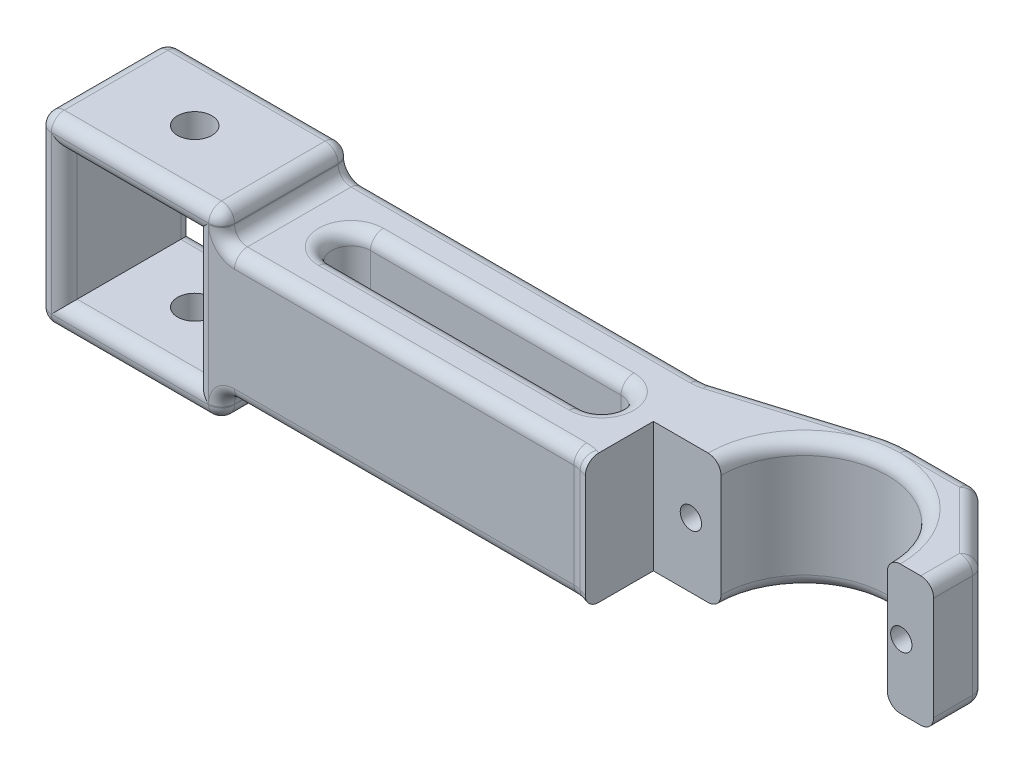
SolidWorks part; units mm, degrees
ref_plane "Front Plane" through (0, 0, 0) normal (0, 0, 1) x (1, 0, 0)
ref_plane "Top Plane" through (0, 0, 0) normal (0, 1, 0) x (1, 0, 0)
ref_plane "Right Plane" through (0, 0, 0) normal (1, 0, 0) x (0, 0, -1)
sketch "Sketch1" plane through (0, 0, 0) normal (0, 0, 1) x (1, 0, 0)
  line L1 (-10.15, -10.15) -> (10.15, -10.15)
  line L2 (-10.15, -10.15) -> (-10.15, 10.15)
  line L3 (-10.15, 10.15) -> (10.15, 10.15)
  line L4 (10.15, -10.15) -> (10.15, 10.15)
  line L5 (-10.15, -10.15) -> (10.15, 10.15) construction
  line L6 (-10.15, 10.15) -> (10.15, -10.15) construction
  point P0 (0, 0)
  dimension "D1" = 20.3
extrude "Extrude-Thin1" add sketch "Sketch1" along normal mid plane 20 thin thin type one direction wall 4
sketch "Sketch2" plane through (0, 0, 0) normal (0, 1, 0) x (1, 0, 0)
  line L3 (14.15, -10) -> (14.15, 10) construction
  line L4 (14.15, 10) -> (69.15, 10)
  line L5 (14.15, 10) -> (14.15, -10)
  line L6 (14.15, -10) -> (69.15, -10)
  line L7 (69.15, 10) -> (69.15, -10)
  line L9 (0, 0) -> (94.15, 0) construction
  line L10 (69.15, -10) -> (89.2407, -16.119)
  line L13 (69.15, 10) -> (89.2407, 16.119)
  line L15 (69.15, -10) -> (69.15, 10)
  circle A2 centre (94.15, 0) radius 12.85
  arc A3 (89.2407, -16.119) -> (89.2407, 16.119) centre (94.15, 0) ccw
  circle A4 centre (94.15, 0) radius 16.85 construction
  dimension "D1" = 25.7
  dimension "D2" = 4
  dimension "D3" = 80
  dimension "D4" = 25
extrude "Boss-Extrude4" add sketch "Sketch2" along normal mid plane 20 contours L7 L4 L5 L6 | L10 A3 L13 L7 A2 region at (41.65, 0, 0) region at (79.3519, 0, -12.5455)
sketch "Sketch3" plane through (0, 0, 0) normal (0, 1, 0) x (1, 0, 0)
  line L0 (94.15, 16.85) -> (114.15, 16.85)
  line L1 (114.15, 16.85) -> (114.15, -16.85)
  line L2 (114.15, -16.85) -> (94.15, -16.85)
  line L3 (14.15, -10) -> (14.15, 10) construction
  arc A1 (94.15, -16.85) -> (94.15, 16.85) centre (94.15, 0) ccw
  arc A2 (89.2407, -16.119) -> (89.2407, 16.119) centre (94.15, 0) ccw construction
  dimension "D1" = 100
extrude "Boss-Extrude5" add sketch "Sketch3" along normal mid plane 20
sketch "Sketch4" plane through (0, 0, 0) normal (0, -1, 0) x (1, 0, 0)
  line L9 (104.15, 16.85) -> (114.15, 16.85)
  line L10 (94.15, 16.85) -> (114.15, 16.85) construction
  line L11 (114.15, 16.85) -> (114.15, 6.85)
  line L12 (114.15, 16.85) -> (114.15, -16.85) construction
  line L13 (114.15, 6.85) -> (104.15, 16.85)
  line L14 (114.15, -16.85) -> (104.15, -16.85)
  line L15 (114.15, -16.85) -> (94.15, -16.85) construction
  line L16 (104.15, -16.85) -> (114.15, -6.85)
  line L17 (114.15, -6.85) -> (114.15, -16.85)
  line L18 (0, 0) -> (114.15, 0) construction
  dimension "D1" = 10
extrude "Cut-Extrude1" cut sketch "Sketch4" against normal through all both and the other way through all contours L13 L9 L11 | L17 L14 L16
sketch "Sketch5" plane through (0, 0, 0) normal (0, 0, 1) x (1, 0, 0)
  line L0 (0, 0) -> (109.15, 0) construction
  line L1 (109.15, 10) -> (109.15, -10) construction
  line L4 (69.15, 10) -> (69.15, -10) construction
  line L5 (104.15, 10) -> (114.15, 10) construction
  circle A0 centre (109.15, 0) radius 1.65
  circle A1 centre (76.65, 0) radius 1.65
  dimension "D1" = 3.3
  dimension "D2" = 3.3
  dimension "D3" = 7.5
extrude "Cut-Extrude2" cut sketch "Sketch5" against normal through all both and the other way through all
fillet "Fillet1" radius 2 6 edges at (14.15, -14.15, 0) (-14.15, -14.15, 0) (-14.15, 14.15, 0) (14.15, 14.15, 0) (14.15, -10, 0) (14.15, 10, 0)
fillet "Fillet2" radius 4 2 edges at (69.15, 0, -10) (69.15, 0, 10)
fillet "Fillet3" radius 2 62 edges at (13.5642, 13.5642, 10) (0, 14.15, 10) (-13.5642, 13.5642, 10) (-14.15, 0, 10) (-13.5642, -13.5642, 10) (0, -14.15, 10) (13.5642, -13.5642, 10) (13.5642, -13.5642, -10) (0, -14.15, -10) (-13.5642, -13.5642, -10) (-14.15, 0, -10) (-13.5642, 13.5642, -10) (0, 14.15, -10) (13.5642, 13.5642, -10) (-10.15, 0, -10) (0, -10.15, -10) (10.15, 0, -10) (0, 10.15, -10) (0, 10.15, 10) (-10.15, 0, 10) (0, -10.15, 10) (10.15, 0, 10) (99.15, -10, 16.85) (99.15, 10, 16.85) (99.15, -10, -16.85) (99.15, 10, -16.85) (104.15, 0, 16.85) (114.15, -10, 0) (114.15, 0, 6.85) (114.15, 10, 0) (42.3522, 10, -10) (69.1435, 10, -10.0436) (79.4802, 10, -13.1463) (91.6683, 10, -16.6662) (42.3522, -10, -10) (69.1435, -10, -10.0436) (79.4802, -10, -13.1463) (91.6683, -10, -16.6662) (42.3522, -10, 10) (69.1435, -10, 10.0436) (79.4802, -10, 13.1463) (91.6683, -10, 16.6662) (42.3522, 10, 10) (69.1435, 10, 10.0436) (79.4802, 10, 13.1463) (91.6683, 10, 16.6662) (104.15, 0, -16.85) (114.15, 0, -6.85) (14.7358, 10.5858, -10) (14.15, 12.075, -10) (14.15, -12.075, -10) (14.7358, -10.5858, -10) (14.7358, -10.5858, 10) (14.15, -12.075, 10) (14.15, 12.075, 10) (14.7358, 10.5858, 10) (109.15, 10, -11.85) (109.15, -10, -11.85) (109.15, -10, 11.85) (109.15, 10, 11.85) (94.15, -10, 12.85) (94.15, 10, 12.85)
sketch "Sketch6" plane through (0, 14.15, 0) normal (0, 1, 0) x (1, 0, 0)
  line L0 (0, 8) -> (0, -8) construction
  line L1 (12.15, 8) -> (-12.15, 8) construction
  line L2 (-12.15, -8) -> (12.15, -8) construction
  circle A2 centre (0, 0) radius 2.65
  dimension "D1" = 5.3
extrude "Cut-Extrude4" cut sketch "Sketch6" against normal through all both and the other way through all
sketch "Sketch7" plane through (0, 0, 0) normal (0, 0, 1) x (1, 0, 0)
  circle A0 centre (109.15, 0) radius 3
  circle A1 centre (76.65, 0) radius 3
  dimension "D1" = 6
extrude "Cut-Extrude5" cut sketch "Sketch7" along normal blind 20 from offset 6
sketch "Sketch8" plane through (0, 0, 0) normal (0, 0, 1) x (1, 0, 0)
  line L1 (76.65, 3.2909) -> (73.8, 1.6454)
  line L2 (73.8, 1.6454) -> (73.8, -1.6454)
  line L3 (73.8, -1.6454) -> (76.65, -3.2909)
  line L4 (76.65, -3.2909) -> (79.5, -1.6454)
  line L5 (79.5, -1.6454) -> (79.5, 1.6454)
  line L6 (79.5, 1.6454) -> (76.65, 3.2909)
  line L7 (109.15, 3.2909) -> (106.3, 1.6454)
  line L8 (106.3, 1.6454) -> (106.3, -1.6454)
  line L9 (106.3, -1.6454) -> (109.15, -3.2909)
  line L10 (109.15, -3.2909) -> (112, -1.6454)
  line L11 (112, -1.6454) -> (112, 1.6454)
  line L12 (112, 1.6454) -> (109.15, 3.2909)
  circle A0 centre (76.65, 0) radius 2.85 construction
  circle A1 centre (109.15, 0) radius 2.85 construction
  dimension "D1" = 5.7
extrude "Cut-Extrude6" cut sketch "Sketch8" against normal blind 20 from offset 5 offset against normal yes
sketch "Sketch9" plane through (0, 0, 0) normal (0, 1, 0) x (1, 0, 0)
  line L0 (70.85, 0) -> (114.15, 0)
  line L2 (114.15, 0) -> (114.15, -21.2033)
  line L3 (114.15, -21.2033) -> (70.85, -21.2033)
  line L4 (70.85, -21.2033) -> (70.85, 0)
  line L6 (114.15, 6.0216) -> (114.15, -6.0216) construction
  dimension "D1" = 43.3
extrude "Cut-Extrude7" cut sketch "Sketch9" against normal through all both and the other way through all
sketch "Sketch10" plane through (0, 10, 0) normal (0, 1, 0) x (1, 0, 0)
  line L0 (24.15, 0) -> (62.85, 0) construction
  line L1 (24.15, 3) -> (62.85, 3)
  line L2 (24.15, -3) -> (62.85, -3)
  line L3 (16.15, 8) -> (16.15, -8) construction
  line L4 (70.85, 0) -> (70.85, -8.4271) construction
  arc A0 (24.15, 3) -> (24.15, -3) centre (24.15, 0) ccw
  arc A1 (62.85, -3) -> (62.85, 3) centre (62.85, 0) ccw
  point P3 (43.5, 0)
  dimension "D1" = 8
  dimension "D2" = 8
  dimension "D3" = 6
extrude "Cut-Extrude8" cut sketch "Sketch10" against normal through all both and the other way through all
fillet "Fillet4" radius 2 8 edges at (43.5, -10, -3) (65.85, -10, 0) (43.5, -10, 3) (43.5, 10, -3) (65.85, 10, 0) (43.5, 10, 3) (21.15, -10, 0) (21.15, 10, 0)
